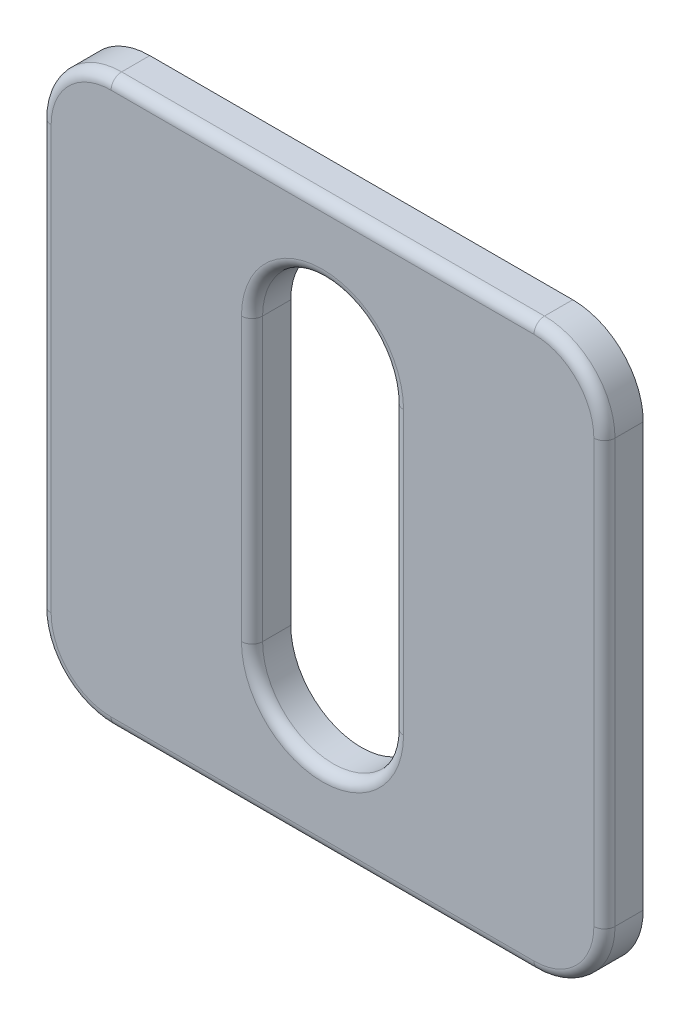
SolidWorks part; units mm, degrees
material "ABS"
ref_plane "Front Plane" through (0, 0, 0) normal (0, 0, 1) x (1, 0, 0)
ref_plane "Top Plane" through (0, 0, 0) normal (0, 1, 0) x (1, 0, 0)
ref_plane "Right Plane" through (0, 0, 0) normal (1, 0, 0) x (0, 0, -1)
sketch "Sketch1" plane through (0, 0, 0) normal (0, 0, 1) x (1, 0, 0)
  line L0 (20, 40) -> (20, 20) construction
  line L1 (0, 0) -> (40, 0)
  line L2 (0, 0) -> (0, 40)
  line L3 (0, 40) -> (40, 40)
  line L4 (40, 0) -> (40, 40)
  line L5 (20, 20) -> (20, 0) construction
  line L6 (20, 30) -> (20, 10) construction
  line L7 (25, 30) -> (25, 10)
  line L8 (15, 30) -> (15, 10)
  arc A0 (25, 30) -> (15, 30) centre (20, 30) ccw
  arc A1 (15, 10) -> (25, 10) centre (20, 10) ccw
  point P10 (20, 20)
  dimension "D3" = 5
  dimension "D1" = 40
  dimension "D2" = 40
extrude "Boss-Extrude1" add sketch "Sketch1" along normal blind 2.75
fillet "Fillet1" radius 5 4 edges at (40, 40, 1.375) (40, 0, 1.375) (0, 0, 1.375) (0, 40, 1.375)
fillet "Fillet2" radius 0.75 12 edges at (1.4645, 1.4645, 2.75) (0, 20, 2.75) (1.4645, 38.5355, 2.75) (38.5355, 38.5355, 2.75) (20, 40, 2.75) (40, 20, 2.75) (38.5355, 1.4645, 2.75) (20, 0, 2.75) (20, 5, 2.75) (25, 20, 2.75) (20, 35, 2.75) (15, 20, 2.75)
